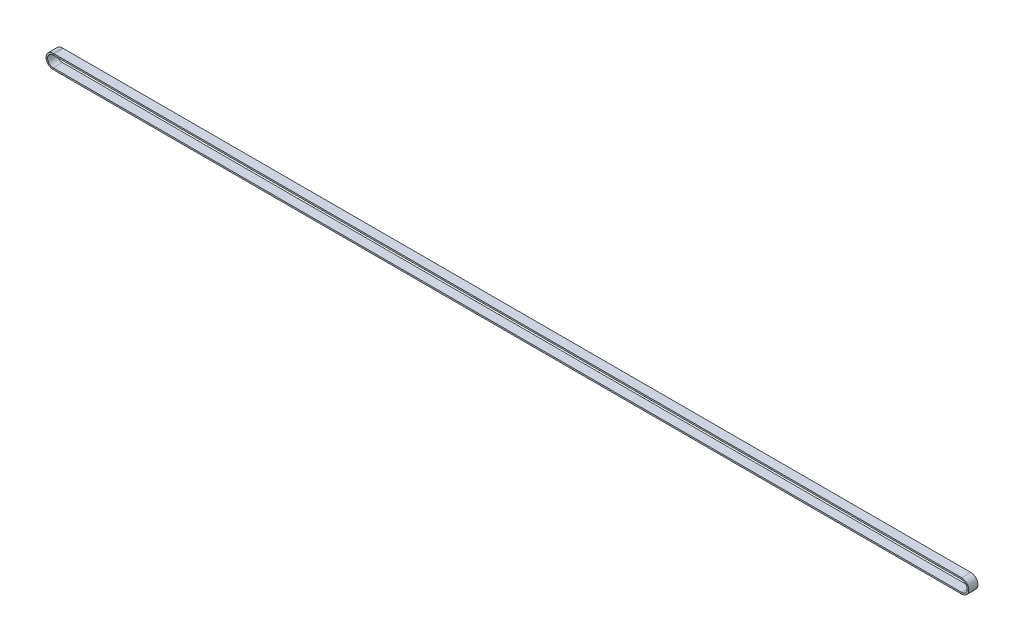
SolidWorks part; units mm, degrees
ref_plane "Front Plane" through (0, 0, 0) normal (0, 0, 1) x (1, 0, 0)
ref_plane "Top Plane" through (0, 0, 0) normal (0, 1, 0) x (1, 0, 0)
ref_plane "Right Plane" through (0, 0, 0) normal (1, 0, 0) x (0, 0, -1)
sketch "Sketch2" plane through (0, 0, -23.7334) normal (0, 0, 1) x (1, 0, 0)
  line L0 (0, 0) -> (1, 0) construction
  line L1 (0, 0) -> (0, 1) construction
  line L2 (-1, -53.5886) -> (883.5206, -53.5886)
  line L3 (883.5206, -67.3886) -> (-1, -67.3886)
  arc A0 (-1, -67.3886) -> (-1, -53.5886) centre (-1, -60.4886) cw
  arc A1 (883.5206, -53.5886) -> (883.5206, -67.3886) centre (883.5206, -60.4886) cw
sketch "Sketch3" plane through (0, 0, 0) normal (1, 0, 0) x (0, 0, -1)
  line L1 (23.7334, -55.0886) -> (14.7334, -55.0886)
  line L2 (23.7334, -55.0886) -> (23.7334, -53.5886)
  line L3 (23.7334, -53.5886) -> (14.7334, -53.5886)
  line L4 (14.7334, -55.0886) -> (14.7334, -53.5886)
  dimension "D1" = 9
  dimension "D2" = 1.5
sweep "Sweep1" add profiles "Sketch3" path "Sketch2"
